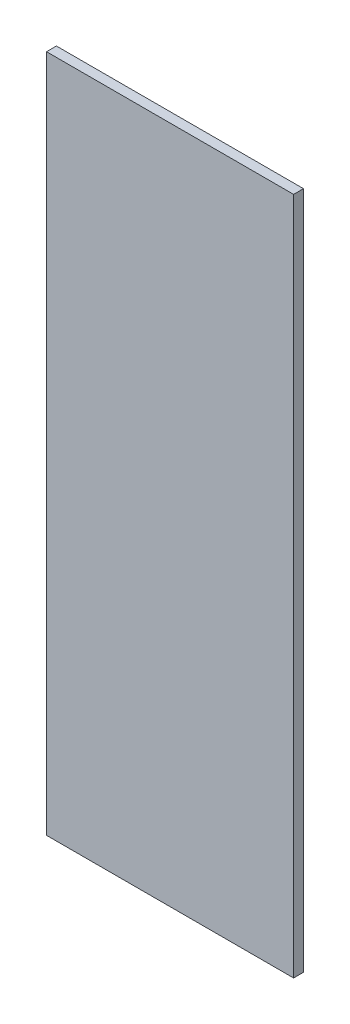
SolidWorks part; units mm, degrees
material "PET"
ref_plane "Front Plane" through (0, 0, 0) normal (0, 0, 1) x (1, 0, 0)
ref_plane "Top Plane" through (0, 0, 0) normal (0, 1, 0) x (1, 0, 0)
ref_plane "Right Plane" through (0, 0, 0) normal (1, 0, 0) x (0, 0, -1)
sketch "Sketch1" plane through (0, 0, 0) normal (0, 0, 1) x (1, 0, 0)
  line L1 (-28.5714, 389.1048) -> (121.4286, 389.1048)
  line L2 (-28.5714, 389.1048) -> (-28.5714, -22.8952)
  line L3 (-28.5714, -22.8952) -> (121.4286, -22.8952)
  line L4 (121.4286, 389.1048) -> (121.4286, -22.8952)
  dimension "D1" = 412
  dimension "D2" = 150
extrude "Boss-Extrude1" add sketch "Sketch1" along normal blind 6
